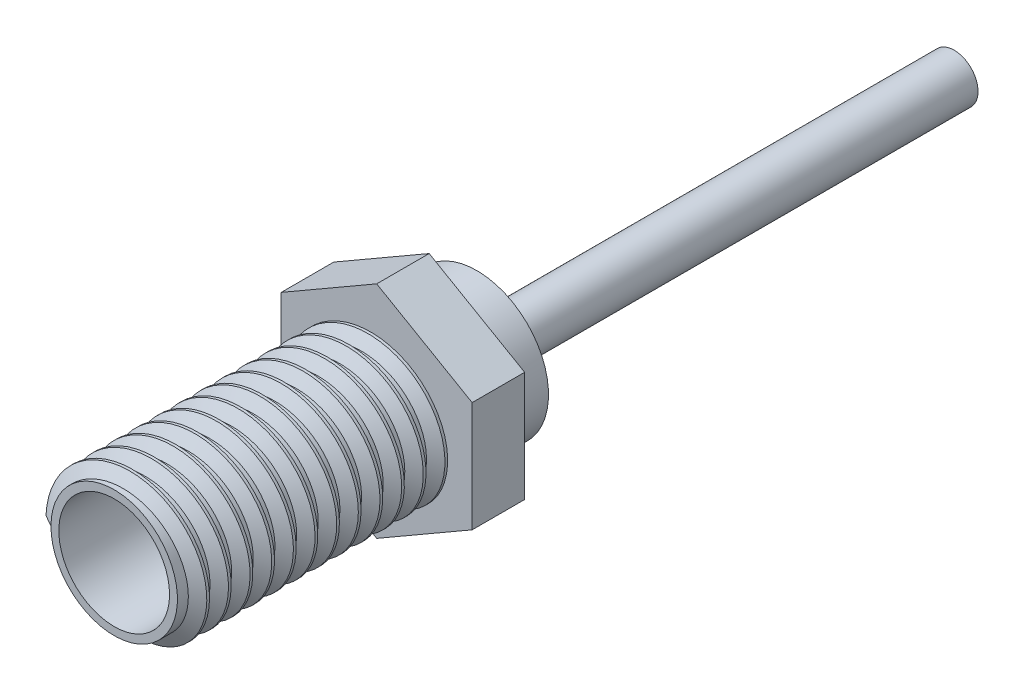
SolidWorks part; units mm, degrees
ref_plane "Front Plane" through (0, 0, 0) normal (0, 0, 1) x (1, 0, 0)
ref_plane "Top Plane" through (0, 0, 0) normal (0, 1, 0) x (1, 0, 0)
ref_plane "Right Plane" through (0, 0, 0) normal (1, 0, 0) x (0, 0, -1)
sketch "Sketch1" plane through (0, 0, 0) normal (0, 0, 1) x (1, 0, 0)
  line L1 (4, 2.3094) -> (0, 4.6188)
  line L2 (0, 4.6188) -> (-4, 2.3094)
  line L3 (-4, 2.3094) -> (-4, -2.3094)
  line L4 (-4, -2.3094) -> (0, -4.6188)
  line L5 (0, -4.6188) -> (4, -2.3094)
  line L6 (4, -2.3094) -> (4, 2.3094)
  circle A0 centre (0, 0) radius 4 construction
  dimension "D1" = 8
extrude "Boss-Extrude1" add sketch "Sketch1" along normal blind 2.2
sketch "Sketch2" plane through (0, 0, 2.2) normal (0, 0, 1) x (1, 0, 0)
  circle A0 centre (0, 0) radius 2.65
  dimension "D1" = 5.3
extrude "Boss-Extrude2" add sketch "Sketch2" along normal blind 11
thread "Thread1" pitch 0.9071 method extrude profile "Thread Profile1" start angle 0, offset 0, length 0, pitch 0.9071, diameter 5.3
ref_plane "Plane1" through (-2.65, 0, 13.2) normal (0, -1, 0) x (-1, 0, 0)
sketch "Thread Profile1" plane through (-2.65, 0, 13.2) normal (0, -1, 0) x (-1, 0, 0)
  line L0 (0, 0) -> (0, 0.9071) construction
  line L1 (0, 0) -> (0.491, 0.2835)
  line L2 (0.491, 0.2835) -> (0.491, 0.3969)
  line L3 (0.491, 0.3969) -> (0, 0.6804)
  line L4 (0.491, 0.3402) -> (0, 0.3402) construction
  line L11 (0, 0) -> (0, 0.6804)
  point P2 (0, 0)
  dimension "Pitch" = 0.9071
  dimension "Profile_Angle" = 60
  dimension "Profile_Land" = 0.1134
  dimension "Profile_Height" = 0.491
sketch "Sketch10" plane through (0, 0, 13.2) normal (0, 0, 1) x (1, 0, 0)
  circle A0 centre (0, 0) radius 2.32
  dimension "D1" = 4.64
extrude "Cut-Extrude1" cut sketch "Sketch10" against normal blind 4
sketch "Sketch11" plane through (0, 0, 9.2) normal (0, 0, 1) x (1, 0, 0)
  circle A0 centre (0, 0) radius 0.75
  dimension "D1" = 1.5
extrude "Cut-Extrude2" cut sketch "Sketch11" against normal blind 4
sketch "Sketch12" plane through (0, 0, 0) normal (0, 0, -1) x (-1, 0, 0)
  circle A0 centre (0, 0) radius 3
  dimension "D1" = 6
extrude "Boss-Extrude3" add sketch "Sketch12" along normal blind 2
sketch "Sketch13" plane through (0, 0, -2) normal (0, 0, -1) x (-1, 0, 0)
  circle A0 centre (0, 0) radius 1
  dimension "D1" = 2
extrude "Boss-Extrude4" add sketch "Sketch13" along normal blind 20
